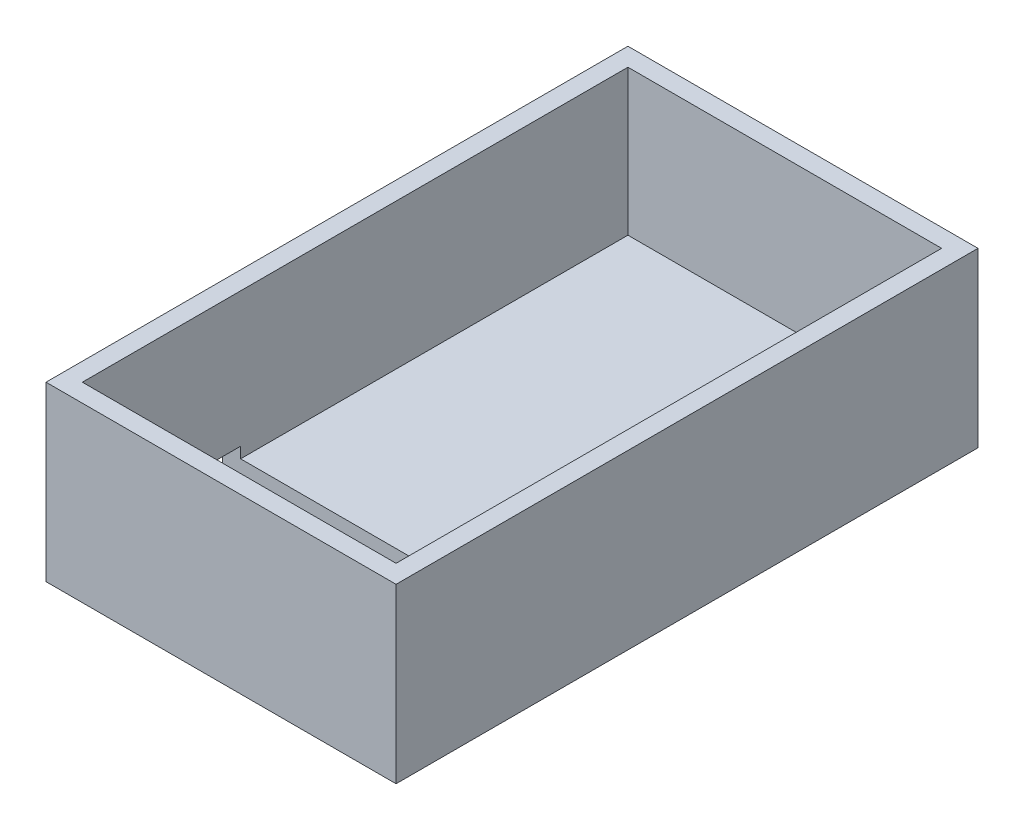
SolidWorks part; units mm, degrees
ref_plane "Front Plane" through (0, 0, 0) normal (0, 0, 1) x (1, 0, 0)
ref_plane "Top Plane" through (0, 0, 0) normal (0, 1, 0) x (1, 0, 0)
ref_plane "Right Plane" through (0, 0, 0) normal (1, 0, 0) x (0, 0, -1)
sketch "Sketch1" plane through (0, 0, 0) normal (0, 1, 0) x (1, 0, 0)
  line L1 (0, 0) -> (34.5, 0)
  line L2 (0, 0) -> (0, 60)
  line L3 (0, 60) -> (34.5, 60)
  line L4 (34.5, 0) -> (34.5, 60)
  dimension "D1" = 60
  dimension "D2" = 34.5
extrude "Boss-Extrude1" add sketch "Sketch1" along normal blind 1
sketch "Sketch2" plane through (0, 0, 0) normal (0, -1, 0) x (1, 0, 0)
  line L4 (0, 0) -> (0, -60)
  line L5 (0, -60) -> (34.5, -60)
  line L6 (34.5, -60) -> (34.5, 0)
  line L7 (34.5, 0) -> (0, 0)
  line L8 (0, 0) -> (0, -60)
  line L9 (0, -60) -> (34.5, -60)
  line L10 (34.5, -60) -> (34.5, 0)
  line L11 (34.5, 0) -> (0, 0)
  line L16 (-2, 2) -> (-2, -62)
  line L17 (-2, -62) -> (36.5, -62)
  line L18 (36.5, -62) -> (36.5, 2)
  line L19 (36.5, 2) -> (-2, 2)
  line L20 (-2, 2) -> (-2, -62)
  line L21 (-2, -62) -> (36.5, -62)
  line L22 (36.5, -62) -> (36.5, 2)
  line L23 (36.5, 2) -> (-2, 2)
  dimension "D1" = 0
  dimension "D2" = 2
extrude "Boss-Extrude2" add sketch "Sketch2" against normal blind 17
sketch "Sketch3" plane through (0, 0, 0) normal (1, 0, 0) x (0, 0, -1)
  line L0 (60, 1) -> (0, 1) construction
  line L1 (17.4041, 1) -> (11.4041, 1)
  line L2 (17.4041, 1) -> (17.4041, 4.2)
  line L3 (17.4041, 4.2) -> (11.4041, 4.2)
  line L4 (11.4041, 1) -> (11.4041, 4.2)
  dimension "D1" = 3.2
  dimension "D2" = 6
extrude "Cut-Extrude1" cut sketch "Sketch3" against normal blind 17
sketch "Sketch4" plane through (0, 1, 0) normal (0, 1, 0) x (1, 0, 0)
  line L0 (-2, 11.4041) -> (0, 11.4041) construction
  line L1 (0, 60) -> (34.5, 60)
  line L2 (0, 60) -> (0, 17.4041)
  line L3 (0, 0) -> (34.5, 0)
  line L4 (34.5, 60) -> (34.5, 0)
  line L5 (0, 17.4041) -> (20, 17.4041)
  line L7 (0, 11.4041) -> (20, 11.4041)
  line L8 (20, 17.4041) -> (20, 11.4041)
  line L9 (0, 11.4041) -> (0, 0)
  dimension "D1" = 20
  dimension "D2" = 0
extrude "Boss-Extrude3" add sketch "Sketch4" along normal blind 2
sketch "Sketch5" plane through (0, 17, 0) normal (0, 1, 0) x (1, 0, 0)
  line L0 (34.5, 0) -> (0, 0) construction
  line L1 (0, 60) -> (34.5, 60) construction
  line L2 (34.5, 60) -> (34.5, 0) construction
  line L3 (34.5, 0) -> (0, 0)
  line L4 (-2, -2) -> (36.5, -2)
  line L5 (36.5, -2) -> (36.5, 62)
  line L6 (36.5, 62) -> (-2, 62)
  line L7 (-2, 62) -> (-2, -2)
  line L8 (-2, -2) -> (36.5, -2)
  line L9 (36.5, -2) -> (36.5, 62)
  line L10 (36.5, 62) -> (-2, 62)
  line L11 (-2, 62) -> (-2, -2)
  line L12 (0, 60) -> (34.5, 60)
  line L13 (34.5, 60) -> (34.5, 0)
  line M5 (34.5, 60) -> (34.5, 0)
  line M6 (34.5, 0) -> (0, 0)
  line M7 (0, 0) -> (0, 60)
  line M8 (0, 60) -> (34.5, 60)
  line M9 (-2, -2) -> (36.5, -2)
  line M10 (36.5, -2) -> (36.5, 62)
  line M11 (36.5, 62) -> (-2, 62)
  line M12 (-2, 62) -> (-2, -2)
  dimension "D1" = 0
extrude "Boss-Extrude4" add sketch "Sketch5" along normal blind 2 contours M12 M9 M10 M11 M8 M5 M6 M7 region at (-1.2531, 17, -30)
chamfer "Chamfer1" distance 2 angle 45 1 edges at (20, 3, -14.4041)
